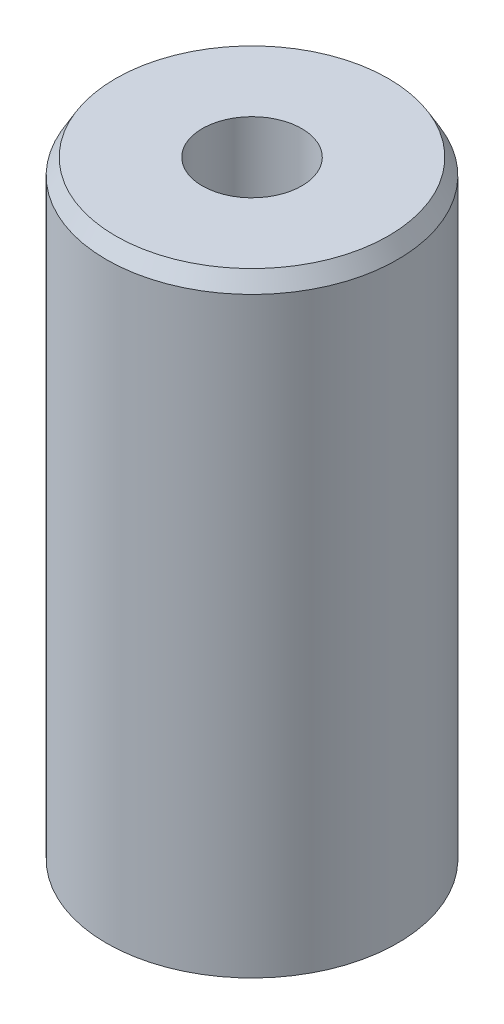
SolidWorks part; units mm, degrees
ref_plane "Front Plane" through (0, 0, 0) normal (0, 0, 1) x (1, 0, 0)
ref_plane "Top Plane" through (0, 0, 0) normal (0, 1, 0) x (1, 0, 0)
ref_plane "Right Plane" through (0, 0, 0) normal (1, 0, 0) x (0, 0, -1)
sketch "Sketch1" plane through (0, 0, 0) normal (0, 1, 0) x (1, 0, 0)
  circle A0 centre (0, 0) radius 42.5
  dimension "SHAFT_OD" = 85
extrude "Boss-Extrude1" add sketch "Sketch1" along normal blind 180.1604
sketch "Sketch2" plane through (0, 0, 0) normal (0, 1, 0) x (1, 0, 0)
  circle A0 centre (0, 0) radius 14.517
  dimension "BORE_D" = 29.0339
extrude "Cut-Extrude1" cut sketch "Sketch2" along normal through all
chamfer "Chamfer1" distance 4.6446 angle 30 2 edges at (0, 180.1604, 42.5) (0, 0, 42.5) first distance on face at (0, 180.1604, 42.5) first distance on face at (0, 0, 14.517)
